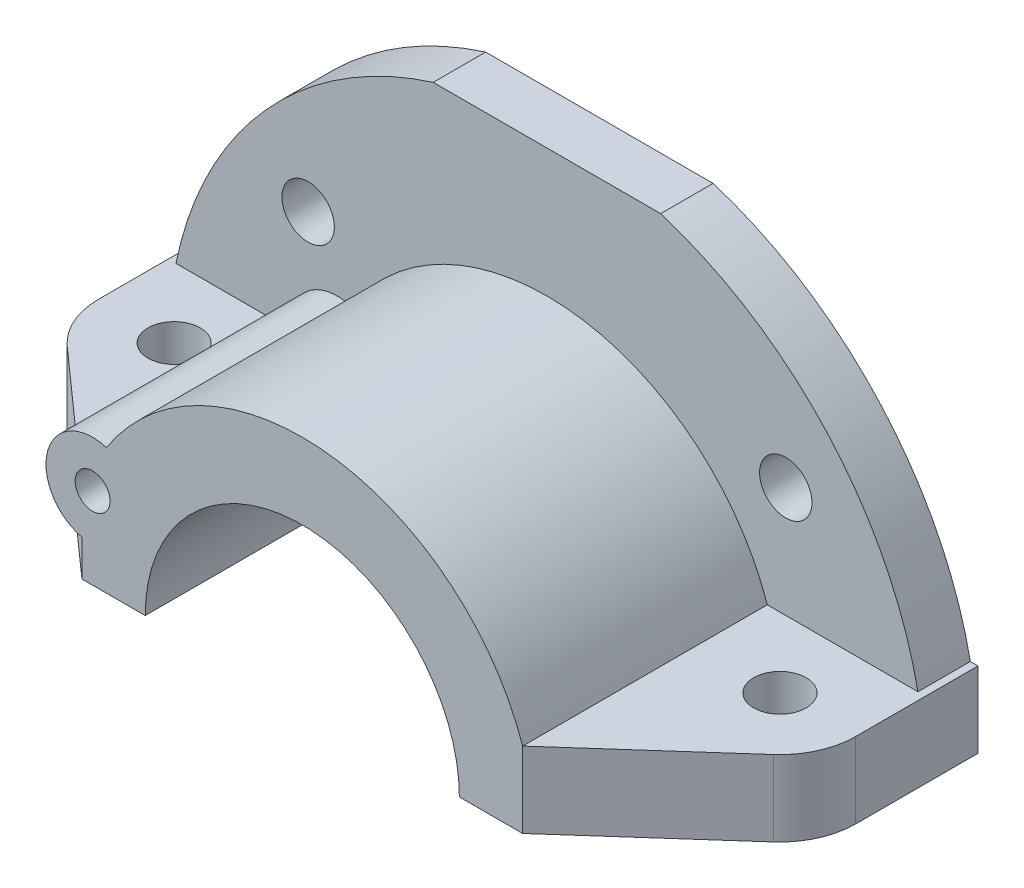
SolidWorks part; units mm, degrees
material "Oak"
ref_plane "Front Plane" through (0, 0, 0) normal (0, 0, 1) x (1, 0, 0)
ref_plane "Top Plane" through (0, 0, 0) normal (0, 1, 0) x (1, 0, 0)
ref_plane "Right Plane" through (0, 0, 0) normal (1, 0, 0) x (0, 0, -1)
sketch "Sketch1" plane through (0, 0, 0) normal (0, 0, 1) x (1, 0, 0)
  line L0 (0, 0) -> (0, -69702.8435) construction
  line L1 (0, 0) -> (-69702.8435, 0) construction
  line L2 (37.8286, 13) -> (65, 13)
  line L3 (-65, 13) -> (-37.8286, 13)
  line L4 (-65, 13) -> (-65, 0)
  line L5 (-65, 0) -> (65, 0)
  line L6 (65, 13) -> (65, 0)
  line L7 (-65, 13) -> (65, 0) construction
  line L8 (-65, 0) -> (65, 13) construction
  line L9 (-19.5192, 62) -> (19.5192, 62)
  arc A0 (63.7129, 12.8713) -> (-63.7129, 12.8713) centre (0, 0) ccw
  arc A1 (40, 0) -> (-40, 0) centre (0, 0) ccw
  arc A2 (26.965, 0) -> (-26.965, 0) centre (0, 0) ccw
  circle A3 centre (-41, 32) radius 4.5
  circle A4 centre (41, 32) radius 4.5
  point P12 (0, 6.5)
  dimension "D1" = 40
  dimension "D2" = 65
  dimension "D3" = 53.93
  dimension "D6" = 32
  dimension "D8" = 9
  dimension "D4" = 65
  dimension "D5" = 13
  dimension "D7" = 41
  dimension "D9" = 62
extrude "Boss-Extrude1" add sketch "Sketch1" along normal blind 51 contours A2 L5 A1 region at (38.5712, 6.4427, 0)
extrude "Boss-Extrude2" add sketch "Sketch1<3>" along normal blind 51 contours A1 L5 L6 L2 | A1 L3 L4 L5 region at (52.134, 6.591, 0) region at (-52.134, 6.591, 0)
sketch "Sketch1<3>" plane through (0, 0, 0) normal (0, 0, 1) x (1, 0, 0) same geometry as "Sketch1"
extrude "Boss-Extrude3" add sketch "Sketch1<4>" along normal blind 9 contours A1 L2 A0 L9 L3 A3 A4 region at (0, 41.3647, 0)
sketch "Sketch1<4>" plane through (0, 0, 0) normal (0, 0, 1) x (1, 0, 0) same geometry as "Sketch1"
sketch "Sketch2" plane through (0, 13, 0) normal (0, 1, 0) x (1, 0, 0)
  line L0 (0, 0) -> (0, -50000) construction
  line L1 (63.6867, 0) -> (19.5192, 0) construction
  line L2 (65, -51) -> (65, 0) construction
  line L3 (37.8286, -51) -> (65, -51) construction
  line L4 (65, -51) -> (65, -21)
  line L5 (37.8286, -51) -> (65, -51)
  line L6 (37.8286, -51) -> (60.639, -30.7143)
  line L7 (-65, -51) -> (-37.8286, -51) construction
  line L8 (-65, -51) -> (-65, 0) construction
  line L9 (-65, -51) -> (-37.8286, -51)
  line L10 (-65, -51) -> (-65, -21)
  line L11 (-37.8286, -51) -> (-60.639, -30.7143)
  arc A0 (60.639, -30.7143) -> (65, -21) centre (52, -21) ccw
  arc A1 (-60.639, -30.7143) -> (-65, -21) centre (-52, -21) cw
  circle A2 centre (52, -21) radius 4.5
  circle A3 centre (-52, -21) radius 4.5
  dimension "D1" = 26
  dimension "D3" = 21
  dimension "D4" = 9
  dimension "D5" = 9
  dimension "D2" = 104
extrude "Cut-Extrude1" cut sketch "Sketch2" against normal up to next
sketch "Sketch3" plane through (0, 0, 51) normal (0, 0, 1) x (1, 0, 0)
  line L0 (-37.8286, 0) -> (-26.965, 0) construction
  circle A0 centre (-36, 14) radius 8
  point P6 (-97.4018, 12.4574)
  dimension "D1" = 16
  dimension "D2" = 14
  dimension "D3" = 36
extrude "Boss-Extrude4" add sketch "Sketch3" against normal up to surface (42 mm away) up to face at (0, 35.8398, 9)
hole_wizard "Ø6.0mm Dowel Hole1" positions "Sketch4" profile "Sketch5" hole size "Ø6.0" standard "AS"
sketch "Sketch4" plane through (0, 0, 51) normal (0, 0, 1) x (1, 0, 0)
  point P0 (-36, 14)
sketch "Sketch5" plane through (-36, 14, 51) normal (1, 0, 0) x (0, -1, 0)
  line L0 (0, 0) -> (0, 13)
  line L1 (0, 13) -> (3, 13)
  line L2 (3, 13) -> (3, 0)
  line L5 (3, 0) -> (0, 0)
  line L10 (0, 13) -> (-3, 13) construction
  line L11 (0, -6.35) -> (0, 107.95) construction
  dimension "Hole Dia." = 6
  dimension "Hole Depth" = 13
  dimension "Drill Angle" = 180
